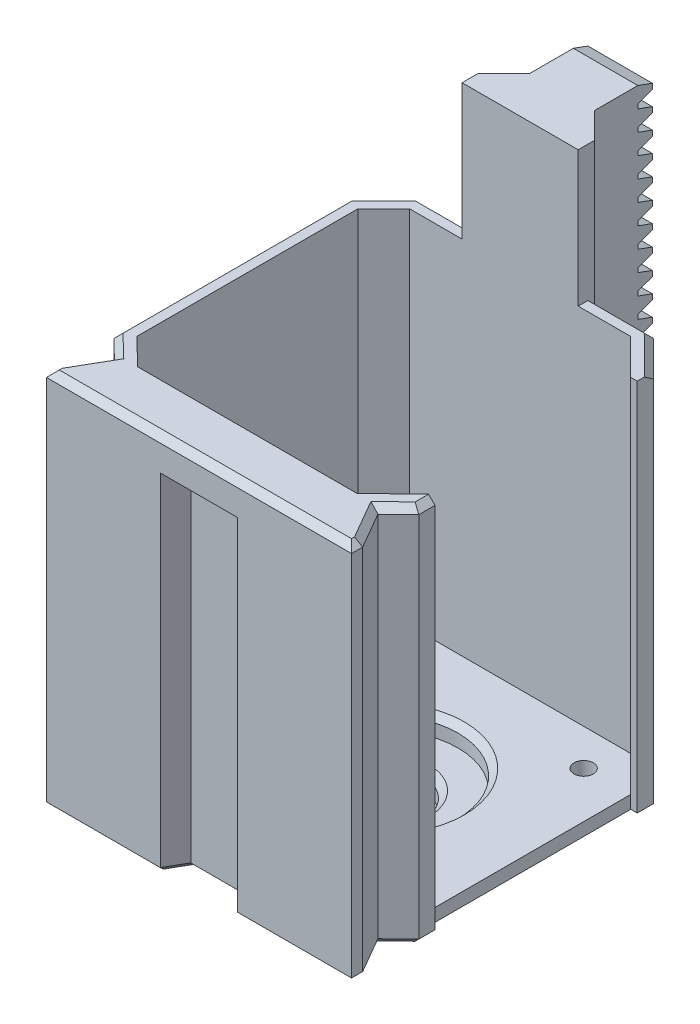
SolidWorks part; units mm, degrees
ref_plane "Front Plane" through (0, 0, 0) normal (0, 0, 1) x (1, 0, 0)
ref_plane "Top Plane" through (0, 0, 0) normal (0, 1, 0) x (1, 0, 0)
ref_plane "Right Plane" through (0, 0, 0) normal (1, 0, 0) x (0, 0, -1)
sketch "Sketch1" plane through (0, 0, 0) normal (0, 1, 0) x (1, 0, 0)
  line L0 (-21.15, 17.15) -> (-17.15, 21.15)
  line L1 (-17, -21.15) -> (17, -21.15)
  line L2 (-21.15, -17.15) -> (-21.15, 17.15)
  line L3 (-17.15, 21.15) -> (17.15, 21.15)
  line L4 (21.15, -17.15) -> (21.15, 17.15)
  line L5 (-21.15, -21.15) -> (21.15, 21.15) construction
  line L6 (-21.15, 21.15) -> (21.15, -21.15) construction
  line L7 (-21.15, -17.15) -> (-17, -21.15)
  line L8 (17, -21.15) -> (21.15, -17.15)
  line L9 (17.15, 21.15) -> (21.15, 17.15)
  circle A0 centre (-15.5, 15.5) radius 1.5
  circle A1 centre (15.5, 15.5) radius 1.5
  circle A2 centre (15.5, -15.5) radius 1.5
  circle A3 centre (-15.5, -15.5) radius 1.5
  circle A4 centre (0, 0) radius 11.5
  point P0 (0, 0)
  dimension "D3" = 3
  dimension "D4" = 3
  dimension "D9" = 3
  dimension "D10" = 3
  dimension "D12" = 23
  dimension "D1" = 42.3
  dimension "D2" = 42.3
  dimension "D11" = 31
  dimension "D13" = 34
  dimension "D6" = 4
  dimension "D7" = 4
extrude "Mount Face Extrude" add sketch "Sketch1" along normal blind 3
chamfer "Bracket Mount Hole Chamfer" distance 0.75 angle 45 4 edges at (-15.5, 0, -14) (15.5, 0, -14) (15.5, 0, 17) (-15.5, 0, 17)
sketch "Sketch5" plane through (0, 0, 0) normal (0, 1, 0) x (1, 0, 0)
  line L0 (21.15, -17.15) -> (22.65, -15.7042)
  line L1 (23.65, -14.7404) -> (23.65, 14.65) construction
  line L3 (-24.65, -28.65) -> (24.65, -28.65) construction
  line L5 (-23.65, -26.9179) -> (-23.65, -28.65)
  line L6 (-23.65, -28.65) -> (23.65, -28.65)
  line L7 (23.65, -28.65) -> (23.65, -26.9179)
  line L8 (-23.65, -26.9179) -> (-24.65, -28.65) construction
  line L9 (24.65, -28.65) -> (23.65, -26.9179) construction
  line L10 (22.65, 15.65) -> (23.65, 15.65)
  line L11 (22.65, -15.7042) -> (23.65, -15.7042)
  line L12 (23.65, 14.65) -> (23.65, 15.65) construction
  line L13 (22.65, 15.65) -> (23.65, 14.65) construction
  line L14 (23.65, -15.7042) -> (23.65, -14.7404) construction
  line L15 (22.65, -15.7042) -> (23.65, -14.7404) construction
  line L16 (-23.65, 18.1855) -> (-23.65, -18.2126)
  line L17 (-23.65, -18.2126) -> (-18.0087, -23.65)
  line L18 (-18.0087, -23.65) -> (18.0087, -23.65)
  line L19 (18.0087, -23.65) -> (23.65, -18.2126)
  line L20 (23.65, -18.2126) -> (23.65, 18.1855)
  line L21 (23.65, 18.1855) -> (18.1855, 23.65)
  line L22 (18.1855, 23.65) -> (-18.1855, 23.65)
  line L23 (-18.1855, 23.65) -> (-23.65, 18.1855)
  line L24 (-23.65, 14.65) -> (-23.65, -18.2126)
  line L25 (-23.65, -18.2126) -> (-20.4209, -21.325)
  line L26 (-18.0087, -23.65) -> (18.0087, -23.65) construction
  line L27 (20.4209, -21.325) -> (23.65, -18.2126)
  line L28 (23.65, -18.2126) -> (23.65, -15.7042)
  line L29 (23.65, 18.1855) -> (18.1855, 23.65)
  line L30 (18.1855, 23.65) -> (-18.1855, 23.65)
  line L31 (-18.1855, 23.65) -> (-23.65, 18.1855)
  line L32 (-21.15, 17.15) -> (-23.65, 14.65) construction
  line L33 (21.15, 17.15) -> (22.65, 15.65)
  line L34 (-23.65, 18.1855) -> (-23.65, 14.65)
  line L35 (23.65, 15.65) -> (23.65, 18.1855)
  line L36 (-23.65, -26.9179) -> (-20.4209, -21.325)
  line L38 (20.4209, -21.325) -> (23.65, -26.9179)
  line L40 (-21.15, 17.15) -> (-21.15, -17.15)
  line L41 (-21.15, -17.15) -> (-17, -21.15)
  line L42 (-17, -21.15) -> (17, -21.15)
  line L43 (17, -21.15) -> (21.15, -17.15)
  line L44 (21.15, -17.15) -> (21.15, 17.15)
  line L45 (21.15, 17.15) -> (17.15, 21.15)
  line L46 (17.15, 21.15) -> (-17.15, 21.15)
  line L47 (-17.15, 21.15) -> (-21.15, 17.15)
  line L48 (-21.15, 17.15) -> (-21.15, -17.15)
  line L49 (-21.15, -17.15) -> (-17, -21.15)
  line L50 (-17, -21.15) -> (17, -21.15)
  line L51 (17, -21.15) -> (21.15, -17.15)
  line L52 (21.15, -17.15) -> (21.15, 17.15) construction
  line L53 (21.15, 17.15) -> (17.15, 21.15)
  line L54 (17.15, 21.15) -> (-17.15, 21.15)
  line L55 (-17.15, 21.15) -> (-21.15, 17.15)
  line L60 (-20.4209, -21.325) -> (-18.0087, -23.65) construction
  line L61 (18.0087, -23.65) -> (20.4209, -21.325) construction
  point P32 (0, -28.65)
  dimension "D3" = 47.3
  dimension "D4" = 60
  dimension "D5" = 47.3
  dimension "D6" = 1
  dimension "D7" = 5
  dimension "D8" = 1
  dimension "D1" = 2.5
  dimension "D2" = 0
extrude "Main Body Extrude" add sketch "Sketch5" along normal blind 59
sketch "Sketch37" plane through (0, 0, 0) normal (0, -1, 0) x (1, 0, 0)
  line L0 (21.15, -17.15) -> (22.65, -15.65) construction
  line L1 (21.15, 17.15) -> (21.15, -17.15) construction
  line L2 (22.65, 15.7042) -> (21.15, 17.15) construction
  line L3 (21.15, -17.15) -> (22.65, -15.65)
  line L4 (21.15, 17.15) -> (21.15, -17.15)
  line L5 (22.65, 15.7042) -> (21.15, 17.15)
  line L6 (22.65, 15.7042) -> (22.65, -15.65)
extrude "Front Face Fill in Extrude" add sketch "Sketch37" against normal up to surface (3 mm away) up to face at (0, 3, 0)
sketch "Sketch39" plane through (0, 0, 0) normal (0, -1, 0) x (1, 0, 0)
  line L0 (-6, 28.65) -> (-4.2679, 25.65)
  line L1 (-23.65, 28.65) -> (23.65, 28.65) construction
  line L2 (-4.2679, 25.65) -> (4.2679, 25.65)
  line L3 (4.2679, 25.65) -> (6, 28.65)
  line L4 (6, 28.65) -> (-6, 28.65)
  line L5 (0, 0) -> (0, 25.65) construction
  dimension "D1" = 3
  dimension "D2" = 12
  dimension "D3" = 60
extrude "Limit Tab" cut sketch "Sketch39" against normal offset from surface (54 mm away) 5 up to face at (2.2864, 59, 4.8477)
sketch "Sketch13" plane through (0, 0, 0) normal (1, 0, 0) x (0, 0, -1)
  line L0 (36.65, 6.9244) -> (36.65, 6.0816)
  line L1 (36.65, 6.0816) -> (34.4, 5.2626)
  line L2 (34.4, 5.2626) -> (34.4, 4.6018)
  line L3 (34.4, 4.6018) -> (36.65, 3.7828)
  line L4 (36.65, 10.066) -> (36.65, 9.2232)
  line L5 (36.65, 9.2232) -> (34.4, 8.4042)
  line L6 (34.4, 8.4042) -> (34.4, 7.7434)
  line L7 (34.4, 7.7434) -> (36.65, 6.9244)
  line L8 (36.65, 13.2076) -> (36.65, 12.3648)
  line L9 (36.65, 12.3648) -> (34.4, 11.5458)
  line L10 (34.4, 11.5458) -> (34.4, 10.885)
  line L11 (34.4, 10.885) -> (36.65, 10.066)
  line L12 (36.65, 16.3492) -> (36.65, 15.5064)
  line L13 (36.65, 15.5064) -> (34.4, 14.6874)
  line L14 (34.4, 14.6874) -> (34.4, 14.0266)
  line L15 (34.4, 14.0266) -> (36.65, 13.2076)
  line L16 (36.65, 19.4908) -> (36.65, 18.648)
  line L17 (36.65, 18.648) -> (34.4, 17.829)
  line L18 (34.4, 17.829) -> (34.4, 17.1681)
  line L19 (34.4, 17.1681) -> (36.65, 16.3492)
  line L20 (36.65, 22.6324) -> (36.65, 21.7895)
  line L21 (36.65, 21.7895) -> (34.4, 20.9706)
  line L22 (34.4, 20.9706) -> (34.4, 20.3097)
  line L23 (34.4, 20.3097) -> (36.65, 19.4908)
  line L24 (36.65, 25.774) -> (36.65, 24.9311)
  line L25 (36.65, 24.9311) -> (34.4, 24.1122)
  line L26 (34.4, 24.1122) -> (34.4, 23.4513)
  line L27 (34.4, 23.4513) -> (36.65, 22.6324)
  line L28 (36.65, 28.9156) -> (36.65, 28.0727)
  line L29 (36.65, 28.0727) -> (34.4, 27.2538)
  line L30 (34.4, 27.2538) -> (34.4, 26.5929)
  line L31 (34.4, 26.5929) -> (36.65, 25.774)
  line L32 (36.65, 32.0572) -> (36.65, 31.2143)
  line L33 (36.65, 31.2143) -> (34.4, 30.3954)
  line L34 (34.4, 30.3954) -> (34.4, 29.7345)
  line L35 (34.4, 29.7345) -> (36.65, 28.9156)
  line L36 (36.65, 35.1988) -> (36.65, 34.3559)
  line L37 (36.65, 34.3559) -> (34.4, 33.537)
  line L38 (34.4, 33.537) -> (34.4, 32.8761)
  line L39 (34.4, 32.8761) -> (36.65, 32.0572)
  line L40 (36.65, 38.3404) -> (36.65, 37.4975)
  line L41 (36.65, 37.4975) -> (34.4, 36.6786)
  line L42 (34.4, 36.6786) -> (34.4, 36.0177)
  line L43 (34.4, 36.0177) -> (36.65, 35.1988)
  line L44 (36.65, 41.482) -> (36.65, 40.6391)
  line L45 (36.65, 40.6391) -> (34.4, 39.8202)
  line L46 (34.4, 39.8202) -> (34.4, 39.1593)
  line L47 (34.4, 39.1593) -> (36.65, 38.3404)
  line L48 (36.65, 44.6235) -> (36.65, 43.7807)
  line L49 (36.65, 43.7807) -> (34.4, 42.9618)
  line L50 (34.4, 42.9618) -> (34.4, 42.3009)
  line L51 (34.4, 42.3009) -> (36.65, 41.482)
  line L52 (36.65, 47.7651) -> (36.65, 46.9223)
  line L53 (36.65, 46.9223) -> (34.4, 46.1034)
  line L54 (34.4, 46.1034) -> (34.4, 45.4425)
  line L55 (34.4, 45.4425) -> (36.65, 44.6235)
  line L56 (36.65, 50.9067) -> (36.65, 50.0639)
  line L57 (36.65, 50.0639) -> (34.4, 49.2449)
  line L58 (34.4, 49.2449) -> (34.4, 48.5841)
  line L59 (34.4, 48.5841) -> (36.65, 47.7651)
  line L60 (36.65, 54.0483) -> (36.65, 53.2055)
  line L61 (36.65, 53.2055) -> (34.4, 52.3865)
  line L62 (34.4, 52.3865) -> (34.4, 51.7257)
  line L63 (34.4, 51.7257) -> (36.65, 50.9067)
  line L64 (36.65, 57.1899) -> (36.65, 56.3471)
  line L65 (36.65, 56.3471) -> (34.4, 55.5281)
  line L66 (34.4, 55.5281) -> (34.4, 54.8673)
  line L67 (34.4, 54.8673) -> (36.65, 54.0483)
  line L68 (36.65, 60.3315) -> (36.65, 59.4887)
  line L69 (36.65, 59.4887) -> (34.4, 58.6697)
  line L70 (34.4, 58.6697) -> (34.4, 58.0089)
  line L71 (34.4, 58.0089) -> (36.65, 57.1899)
  line L72 (36.65, 63.4731) -> (36.65, 62.6302)
  line L73 (36.65, 62.6302) -> (34.4, 61.8113)
  line L74 (34.4, 61.8113) -> (34.4, 61.1504)
  line L75 (34.4, 61.1504) -> (36.65, 60.3315)
  line L76 (36.65, 66.6147) -> (36.65, 65.7718)
  line L77 (36.65, 65.7718) -> (34.4, 64.9529)
  line L78 (34.4, 64.9529) -> (34.4, 64.292)
  line L79 (34.4, 64.292) -> (36.65, 63.4731)
  line L80 (36.65, 69.7563) -> (36.65, 68.9134)
  line L81 (36.65, 68.9134) -> (34.4, 68.0945)
  line L82 (34.4, 68.0945) -> (34.4, 67.4336)
  line L83 (34.4, 67.4336) -> (36.65, 66.6147)
  line L84 (36.65, 72.8979) -> (36.65, 72.055)
  line L85 (36.65, 72.055) -> (34.4, 71.2361)
  line L86 (34.4, 71.2361) -> (34.4, 70.5752)
  line L87 (34.4, 70.5752) -> (36.65, 69.7563)
  line L88 (36.65, 76.0395) -> (36.65, 75.1966)
  line L89 (36.65, 75.1966) -> (34.4, 74.3777)
  line L90 (34.4, 74.3777) -> (34.4, 73.7168)
  line L91 (34.4, 73.7168) -> (36.65, 72.8979)
  line L92 (36.65, 79.1811) -> (36.65, 78.3382)
  line L93 (36.65, 78.3382) -> (34.4, 77.5193)
  line L94 (34.4, 77.5193) -> (34.4, 76.8584)
  line L95 (34.4, 76.8584) -> (36.65, 76.0395)
  line L98 (36.65, 3.7828) -> (36.65, 2.94)
  line L99 (36.65, 2.94) -> (34.4, 2.1211)
  line L100 (34.4, 2.1211) -> (34.4, 1.4602)
  line L101 (34.4, 1.4602) -> (36.65, 0.6413)
  line L102 (36.65, 0.6413) -> (36.65, 0)
  line L103 (36.65, 0) -> (23.65, 0)
  line L104 (23.65, 0) -> (23.65, 80)
  line L105 (23.65, 59) -> (23.65, 0) construction
  line L106 (23.65, 80) -> (34.4, 80)
  line L108 (34.4, 80) -> (36.65, 79.1811)
  line L147 (18.1855, 0) -> (23.65, 0) construction
  line L148 (34.4, 80.6609) -> (34.4, 80) [skipped]
  line L149 (36.65, 81.4798) -> (34.4, 80.6609) [skipped]
  line L150 (36.65, 82.3227) -> (36.65, 81.4798) [skipped]
  line L151 (34.4, 83.1416) -> (36.65, 82.3227) [skipped]
  line L152 (36.65, 84.6214) -> (34.4, 83.8025) [skipped]
  line L153 (34.4, 86.2832) -> (36.65, 85.4643) [skipped]
  line L154 (36.65, 87.763) -> (34.4, 86.9441) [skipped]
  line L155 (34.4, 89.4248) -> (36.65, 88.6058) [skipped]
  line L156 (36.65, 90.9046) -> (34.4, 90.0856) [skipped]
  line L157 (34.4, 92.5664) -> (36.65, 91.7474) [skipped]
  line L158 (34.4, 83.8025) -> (34.4, 83.1416) [skipped]
  line L159 (34.4, 86.9441) -> (34.4, 86.2832) [skipped]
  line L160 (36.65, 85.4643) -> (36.65, 84.6214) [skipped]
  line L161 (36.65, 88.6058) -> (36.65, 87.763) [skipped]
  line L162 (34.4, 90.0856) -> (34.4, 89.4248) [skipped]
  line L163 (36.65, 91.7474) -> (36.65, 90.9046) [skipped]
  line L164 (34.4, 93.2272) -> (34.4, 92.5664) [skipped]
  line L165 (36.65, 94.0462) -> (34.4, 93.2272) [skipped]
  line L166 (36.65, 94.889) -> (36.65, 94.0462) [skipped]
  line L167 (34.4, 95.708) -> (36.65, 94.889) [skipped]
  line L168 (34.4, 96.3688) -> (34.4, 95.708) [skipped]
  line L169 (36.65, 97.1878) -> (34.4, 96.3688) [skipped]
  line L170 (36.65, 98.0306) -> (36.65, 97.1878) [skipped]
  line L171 (34.4, 98.8496) -> (36.65, 98.0306) [skipped]
  line L172 (34.4, 99.5104) -> (34.4, 98.8496) [skipped]
  line L173 (36.65, 100.3294) -> (34.4, 99.5104) [skipped]
  line L174 (36.65, 101.1722) -> (36.65, 100.3294) [skipped]
  line L175 (34.4, 101.9911) -> (36.65, 101.1722) [skipped]
  line L176 (34.4, 102.652) -> (34.4, 101.9911) [skipped]
  line L177 (36.65, 110.597) -> (36.65, 109.7541) [skipped]
  line L178 (36.65, 109.7541) -> (34.4, 108.9352) [skipped]
  line L179 (34.4, 108.9352) -> (34.4, 108.2743) [skipped]
  line L180 (34.4, 108.2743) -> (36.65, 107.4554) [skipped]
  line L181 (36.65, 107.4554) -> (36.65, 106.6125) [skipped]
  line L182 (36.65, 106.6125) -> (34.4, 105.7936) [skipped]
  line L183 (34.4, 105.7936) -> (34.4, 105.1327) [skipped]
  line L184 (34.4, 105.1327) -> (36.65, 104.3138) [skipped]
  line L185 (36.65, 104.3138) -> (36.65, 103.471) [skipped]
  line L186 (36.65, 103.471) -> (34.4, 102.652) [skipped]
  point P14 (23.65, 80)
  dimension "D1" = 80
  dimension "D2" = 0.8429
  dimension "D3" = 0.6609
  dimension "D4" = 2.2987
  dimension "D5" = 13
  dimension "D6" = 0.6413
  dimension "D7" = 20
  dimension "D8" = 3.1416
  dimension "D9" = 35
extrude "Rack Extrude" add sketch "Sketch13" against normal mid plane 10
sketch "Rack Line" plane through (0, 0, 0) normal (1, 0, 0) x (0, 0, -1)
  line L0 (35.65, 0) -> (35.65, 80)
  line L1 (23.65, 0) -> (36.65, 0) construction
  line L3 (23.65, 59) -> (23.65, 0) construction
  dimension "D1" = 12
chamfer "Rack Chamfer" distance 4 angle 45 2 edges at (5, 29.5, -23.65) (-5, 29.5, -23.65)
sketch "Sketch15" plane through (0, 59, 0) normal (0, 1, 0) x (1, 0, 0)
  line L0 (-5, 27.65) -> (-9, 23.65)
  line L1 (17.15, 21.15) -> (-17.15, 21.15) construction
  line L2 (-9, 21.15) -> (9, 21.15)
  line L3 (9, 23.65) -> (5, 27.65)
  line L4 (5, 27.65) -> (-5, 27.65)
  line L5 (9, 23.65) -> (5, 27.65) construction
  line L6 (-5, 27.65) -> (-9, 23.65) construction
  line L9 (-9, 23.65) -> (-9, 21.15)
  line L10 (9, 23.65) -> (9, 21.15)
  line L11 (-11.5, 21.15) -> (-9, 21.15) construction
  line L12 (-9, 23.65) -> (-11.5, 21.15) construction
  line L13 (9, 21.15) -> (11.5, 21.15) construction
  line L14 (11.5, 21.15) -> (9, 23.65) construction
  line L15 (-9, 23.65) -> (-18.1855, 23.65) construction
  line L16 (-5, 27.65) -> (-5, 36.65) construction
extrude "Rack Support Base Extrude" add sketch "Sketch15" along normal up to surface (21 mm away) up to face at (0, 80, -29.025)
sketch "Sketch27" plane through (0, 0, 0) normal (0, -1, 0) x (-1, 0, 0)
  circle A4 centre (0, 0) radius 13.6
  circle A5 centre (0, 0) radius 11.5 construction
  circle A6 centre (0, 0) radius 11.5
  circle A7 centre (0, 0) radius 6
  circle M47 centre (0, 0) radius 11.5
  dimension "D1" = 12
  dimension "D4" = 27.2
extrude "Face Cosmetic Ring Extrude" add sketch "Sketch27" along normal blind 4 contours A4 M47 | A7 M47 region at (13.2153, 0, 0) region at (11.1747, 0, 0)
chamfer "Face Cosmetic Ring Main Chamfer" distance 4 angle 45 1 edges at (0, 0, -13.6)
chamfer "Face Cosmetic Ring Main Through Hole Chamfer" distance 1 angle 45 3 edges at (0, -4, -6) (0, 0, -6) (0, 3, 11.5)
chamfer "Front/Back Face Chamfer" distance 1 angle 45 36 edges at (13.5928, 59, -23.65) (20.9178, 59, -20.9178) (23.65, 59, 16.9584) (22.0354, 59, 19.7688) (0, 59, 28.65) (-22.0354, 59, 19.7688) (-23.65, 59, 0.0135) (-20.9178, 59, -20.9178) (-13.5928, 59, -23.65) (-7, 0, -25.65) (-13.5928, 0, -23.65) (-20.9178, 0, -20.9178) (7, 0, -25.65) (13.5928, 0, -23.65) (20.9178, 0, -20.9178) (23.65, 0, -16.9178) (23.15, 0, -15.65) (22.65, 0, 0.0271) (23.15, 0, 15.7042) (23.65, 0, 16.9584) (22.0354, 0, 19.7688) (14.825, 0, 28.65) (5.134, 0, 27.15) (0, 0, 25.65) (-5.134, 0, 27.15) (-14.825, 0, 28.65) (-22.0354, 0, 19.7688) (-23.65, 0, 0.0135) (23.65, 59, 27.784) (-23.65, 59, 27.784) (23.65, 0, 27.784) (-23.65, 0, 27.784) (22.0354, 0, 24.1215) (-22.0354, 0, 24.1215) (22.0354, 59, 24.1215) (-22.0354, 59, 24.1215)
